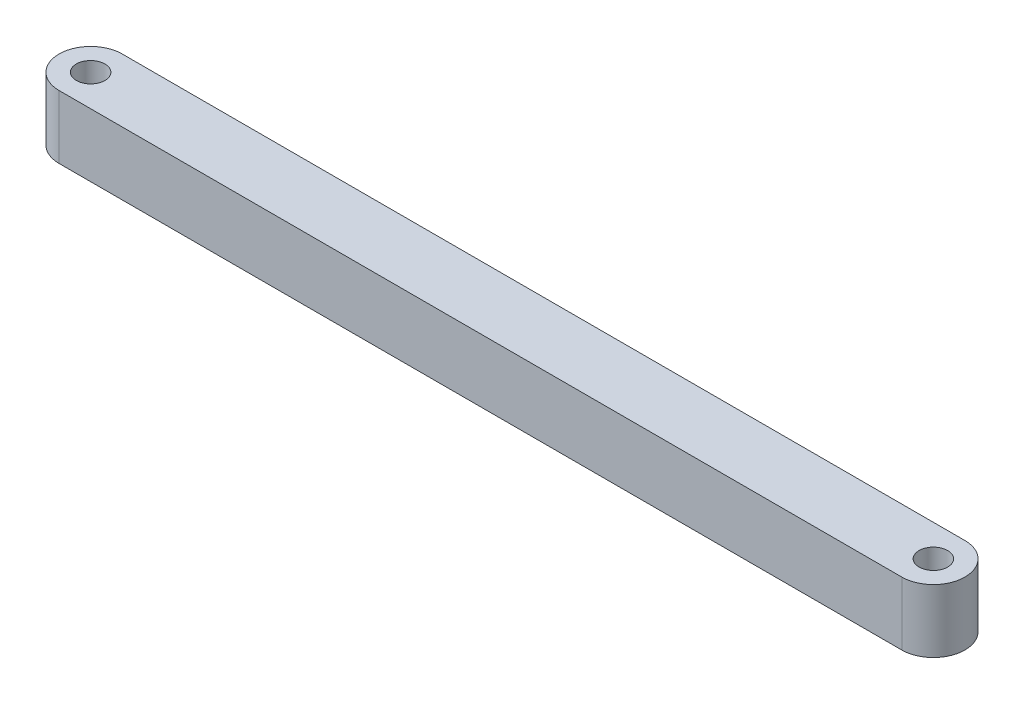
SolidWorks part; units mm, degrees
ref_plane "Front Plane" through (0, 0, 0) normal (0, 0, 1) x (1, 0, 0)
ref_plane "Top Plane" through (0, 0, 0) normal (0, 1, 0) x (1, 0, 0)
ref_plane "Right Plane" through (0, 0, 0) normal (1, 0, 0) x (0, 0, -1)
sketch "Sketch1" plane through (0, 0, 0) normal (0, 1, 0) x (1, 0, 0)
  line L0 (0, 0) -> (127, 0) construction
  line L1 (0, 4.7625) -> (127, 4.7625)
  line L2 (0, -4.7625) -> (127, -4.7625)
  arc A0 (0, 4.7625) -> (0, -4.7625) centre (0, 0) ccw
  arc A1 (127, -4.7625) -> (127, 4.7625) centre (127, 0) ccw
  point P3 (63.5, 0)
  dimension "D1" = 127
  dimension "D2" = 9.525
extrude "Boss-Extrude1" add sketch "Sketch1" along normal mid plane 9.525
sketch "Sketch2" plane through (0, 4.7625, 0) normal (0, 1, 0) x (1, 0, 0)
  circle A0 centre (0, 0) radius 2.159
  circle A1 centre (127, 0) radius 2.159
  dimension "D1" = 4.318
  dimension "D2" = 4.318
extrude "Cut-Extrude1" cut sketch "Sketch2" against normal through all
